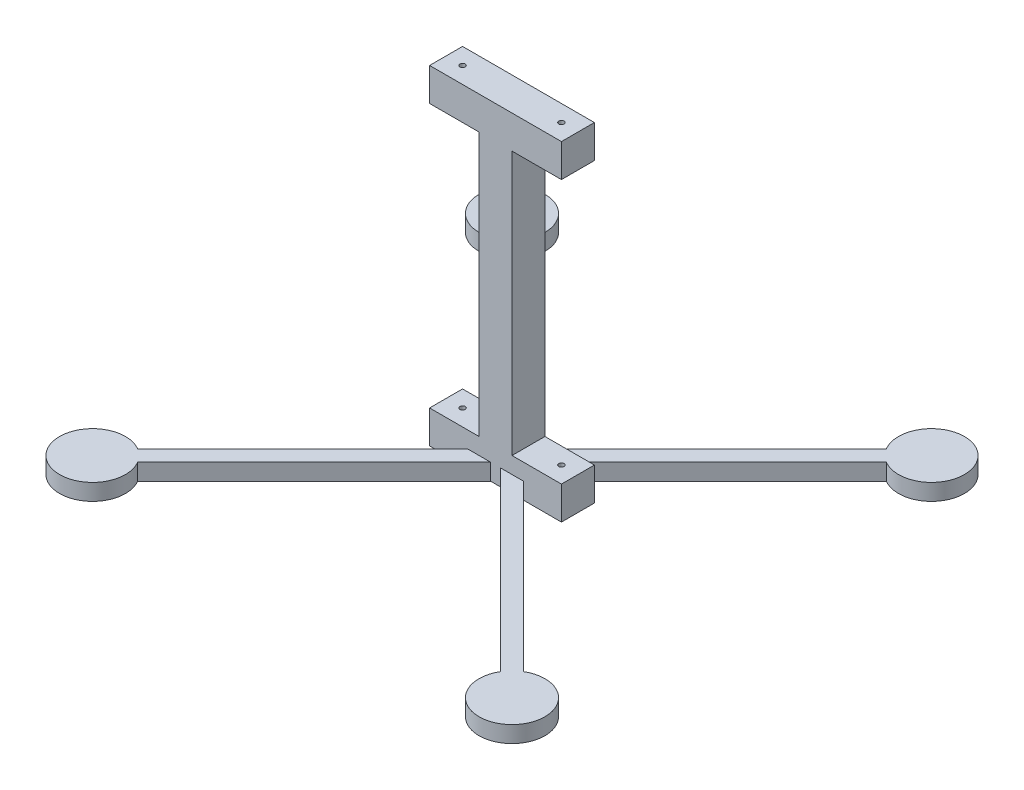
SolidWorks part; units mm, degrees
ref_plane "前视基准面" through (0, 0, 0) normal (0, 0, 1) x (1, 0, 0)
ref_plane "上视基准面" through (0, 0, 0) normal (0, 1, 0) x (1, 0, 0)
ref_plane "右视基准面" through (0, 0, 0) normal (1, 0, 0) x (0, 0, -1)
sketch "草图1" plane through (0, 0, 0) normal (0, 0, 1) x (1, 0, 0)
  line L0 (0, 153.3898) -> (0, -167.3729) construction
  line L1 (-20, 10) -> (20, 10)
  line L2 (20, 10) -> (20, 0)
  line L3 (20, 0) -> (5, 0)
  line L4 (5, 0) -> (5, -80)
  line L5 (5, -80) -> (20, -80)
  line L6 (20, -80) -> (20, -90)
  line L7 (20, -90) -> (-20, -90)
  line L8 (-20, -80) -> (-20, -90)
  line L9 (-5, -80) -> (-20, -80)
  line L10 (-5, 0) -> (-5, -80)
  line L11 (-20, 0) -> (-5, 0)
  line L12 (-20, 10) -> (-20, 0)
  point P13 (0, -90)
  point P18 (0, 10)
  dimension "D1" = 100
  dimension "D2" = 20
  dimension "D3" = 5
  dimension "D4" = 20
  dimension "D5" = 10
  dimension "D6" = 10
extrude "凸台-拉伸1" add sketch "草图1" along normal mid plane 10
sketch "草图2" plane through (0, -90, 0) normal (0, -1, 0) x (1, 0, 0)
  line L0 (0, 65.8243) -> (0, 0) construction
  line L1 (0, 0) -> (98.9183, 0) construction
  line L2 (62.8668, 62.8668) -> (0, 0) construction
  line L3 (65.4074, 61.8718) -> (61.8718, 65.4074)
  line L4 (61.8718, 65.4074) -> (-1.7678, 1.7678)
  line L5 (-1.7678, 1.7678) -> (1.7678, -1.7678)
  line L6 (65.4074, 61.8718) -> (1.7678, -1.7678)
  point P10 (63.6396, 63.6396)
  dimension "D1" = 45
  dimension "D2" = 5
  dimension "D3" = 90
extrude "凸台-拉伸2" add sketch "草图2" against normal blind 5
ref_axis "基准轴1" through (0, 27.5, 0) along (0, -1, 0)
pattern_circular "阵列(圆周)1" count 4 every 90 about axis through (0, 27.5, 0) along (0, -1, 0) of "凸台-拉伸2"
sketch "草图3" plane through (0, -85, 0) normal (0, 1, 0) x (1, 0, 0)
  line L0 (61.8718, 65.4074) -> (65.4074, 61.8718) construction
  circle A0 centre (63.6396, 63.6396) radius 10
  dimension "D1" = 20
extrude "凸台-拉伸3" add sketch "草图3" against normal up to surface (5 mm away) up to face at (0, -90, 0)
pattern_circular "阵列(圆周)2" count 4 every 90 about axis through (0, 27.5, 0) along (0, -1, 0) of "凸台-拉伸3"
sketch "草图4" plane through (0, 10, 0) normal (0, 1, 0) x (1, 0, 0)
  line L0 (0, 40.9) -> (0, 0) construction
  line L1 (0, 0) -> (41.4663, 0) construction
  circle A0 centre (15, 0) radius 0.8
  circle A1 centre (-15, 0) radius 0.8
  dimension "D1" = 1.6
  dimension "D2" = 15
extrude "切除-拉伸1" cut sketch "草图4" against normal blind 219
